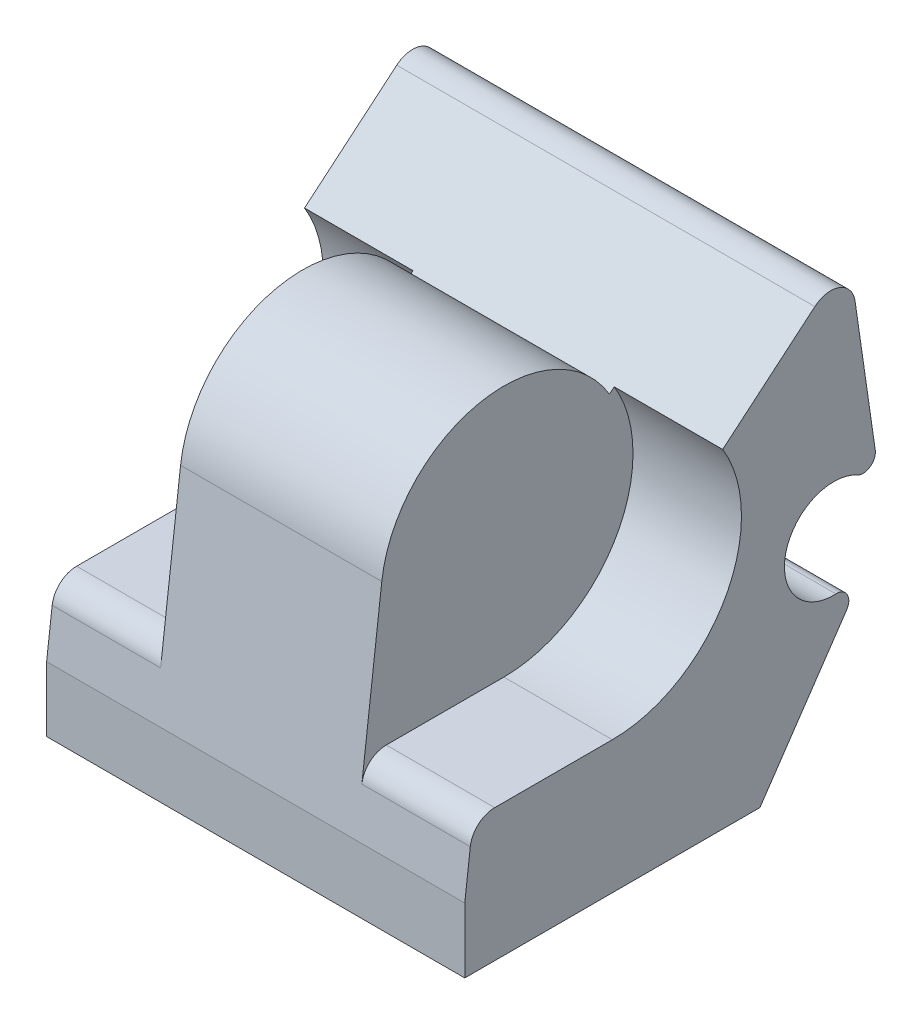
SolidWorks part; units mm, degrees
ref_plane "Front Plane" through (0, 0, 0) normal (0, 0, 1) x (1, 0, 0)
ref_plane "Top Plane" through (0, 0, 0) normal (0, 1, 0) x (1, 0, 0)
ref_plane "Right Plane" through (0, 0, 0) normal (1, 0, 0) x (0, 0, -1)
sketch "Sketch1" plane through (0, 0, 0) normal (1, 0, 0) x (0, 0, -1)
  line L0 (-15.761, 1.8989) -> (-19.05, -25.4)
  line L1 (15.761, 1.8989) -> (19.05, -25.4)
  line L2 (-19.05, -25.4) -> (-19.05, -33.782)
  line L3 (-19.05, -33.782) -> (19.05, -33.782)
  line L4 (19.05, -33.782) -> (19.05, -25.4)
  arc A0 (15.761, 1.8989) -> (-15.761, 1.8989) centre (0, 0) ccw
  circle A1 centre (0, 0) radius 15.875 construction
  dimension "D1" = 31.75
  dimension "D2" = 33.782
  dimension "D3" = 25.4
  dimension "D4" = 38.1
extrude "Boss-Extrude1" add sketch "Sketch1" along normal mid plane 53.975
sketch "Sketch2" plane through (0, 0, 0) normal (1, 0, 0) x (0, 0, -1)
  line L0 (3.9515, 0.0055) -> (13.6257, 8.1458) construction
  line L2 (0, 0) -> (3.9515, 0.0055) construction
  line L5 (24.1248, 18.0177) -> (24.6358, 17.4103) construction
  line L6 (34.8498, -7.5467) -> (31.3317, 16.7069)
  line L7 (26.1454, 18.6805) -> (30.5124, 22.3552) construction
  line L8 (30.5124, 22.3552) -> (31.3317, 16.7069) construction
  line L9 (33.8194, -12.0246) -> (19.05, -33.782)
  line L10 (19.05, -33.782) -> (19.05, -25.4)
  line L11 (11.2594, -12.2912) -> (3.9515, 0.0055) construction
  line L12 (0, 15.875) -> (0, 16.6688) construction
  line L13 (19.05, -25.4) -> (11.2594, -12.2912) construction
  line L14 (14.2406, 8.6632) -> (13.6257, 8.1458) construction
  line L15 (13.6257, 8.1458) -> (26.1454, 18.6805)
  line L17 (19.05, -25.4) -> (15.761, 1.8989)
  line L18 (19.05, -33.782) -> (19.05, -25.4) construction
  line L19 (15.761, 1.8989) -> (19.05, -25.4) construction
  line L20 (31.3422, 15.875) -> (5.0825, 15.875) construction
  line L21 (0, 0) -> (25.7629, 21.6783) construction
  circle A0 centre (28.5655, -8.4582) radius 3.175
  arc A2 (12.6144, 9.6381) -> (13.6257, 8.1458) centre (0, 0) ccw construction
  arc A3 (13.6158, 8.1624) -> (12.6144, 9.6381) centre (0, 0) ccw construction
  arc A4 (31.3317, 16.7069) -> (26.1454, 18.6805) centre (28.1896, 16.2512) ccw
  arc A5 (33.8194, -12.0246) -> (34.8498, -7.5467) centre (28.5655, -8.4582) ccw
  arc A6 (34.8498, -7.5467) -> (33.8194, -12.0246) centre (28.5655, -8.4582) ccw construction
  arc A7 (26.1454, 18.6805) -> (31.3317, 16.7069) centre (28.1896, 16.2512) ccw construction
  circle A9 centre (0, 0) radius 16.6688 construction
  arc A13 (12.6144, 9.6381) -> (13.6158, 8.1624) centre (0, 0) cw construction
  arc A14 (13.6257, 8.1458) -> (13.6158, 8.1624) centre (0, 0) ccw construction
  arc A17 (13.6257, 8.1458) -> (15.761, 1.8989) centre (0, 0) cw
  arc A18 (15.761, 1.8989) -> (-15.761, 1.8989) centre (0, 0) ccw construction
  arc A19 (13.6158, 8.1624) -> (13.6257, 8.1458) centre (0, 0) cw construction
  dimension "D3" = 6.35
  dimension "D8" = 6.35
  dimension "D9" = 12.7
  dimension "D1" = 2.54
  dimension "D2" = 8.4582
  dimension "D5" = 123.209
  dimension "D6" = 40
extrude "Boss-Extrude2" add sketch "Sketch2" along normal mid plane 53.975
ref_plane "Plane1" through (20.6375, 0, 0) normal (1, 0, 0) x (0, 0, -1)
ref_plane "Plane2" through (-21.9075, 0, 0) normal (-1, 0, 0) x (0, 0, 1)
sketch "Sketch3" plane through (26.9875, 0, 0) normal (1, 0, 0) x (0, 0, -1)
  line L1 (-15.761, 1.8989) -> (-19.05, -25.4) construction
  line L5 (-15.1826, -16.6687) -> (0, -16.6687)
  line L6 (-15.761, 1.8989) -> (-18.3348, -19.464)
  line L7 (14.2406, 8.6632) -> (13.6257, 8.1458)
  line L8 (26.1454, 18.6805) -> (13.6257, 8.1458) construction
  arc A0 (13.6257, 8.1458) -> (-15.761, 1.8989) centre (0, 0) ccw
  arc A2 (0, -16.6687) -> (14.2406, 8.6632) centre (0, 0) ccw
  arc A3 (-15.1826, -16.6687) -> (-18.3348, -19.464) centre (-15.1826, -19.8438) ccw
  arc A4 (14.2406, 8.6632) -> (-16.369, -3.1471) centre (0, 0) ccw construction
  arc A5 (-15.761, 1.8989) -> (13.6257, 8.1458) centre (0, 0) ccw construction
  arc A6 (-16.369, -3.1471) -> (0, -16.6687) centre (0, 0) ccw construction
  arc A7 (-18.3348, -19.464) -> (-15.1826, -16.6687) centre (-15.1826, -19.8438) ccw construction
  arc A8 (13.6257, 8.1458) -> (-15.761, 1.8989) centre (0, 0) ccw construction
  dimension "D1" = 0.7937
  dimension "D2" = 6.35
extrude "Cut-Extrude1" cut sketch "Sketch3" against normal blind 14
extrude "Cut-Extrude2" cut sketch "Sketch3<3>" along normal blind 14 from surface starting at face at (-26.9875, -6.1299, -11.5252)
sketch "Sketch3<3>" plane through (26.9875, 0, 0) normal (1, 0, 0) x (0, 0, -1) same geometry as "Sketch3"
sketch "Sketch4" plane through (26.9875, 0, 0) normal (1, 0, 0) x (0, 0, -1)
  line L0 (19.05, -33.782) -> (33.8194, -12.0246) construction
  line L1 (34.8498, -7.5467) -> (31.3317, 16.7069) construction
  line L2 (33.8194, -12.0246) -> (30.2529, -17.2785)
  line L3 (33.9382, -1.2624) -> (34.8498, -7.5467)
  arc A0 (33.8194, -12.0246) -> (34.8498, -7.5467) centre (28.5655, -8.4582) ccw
  arc A3 (31.6068, -2.8839) -> (33.9382, -1.2624) centre (32.3672, -1.4903) ccw
  arc A4 (30.2529, -17.2785) -> (28.8647, -14.8011) centre (28.9395, -16.3869) ccw
  arc A5 (33.9382, -1.2624) -> (31.6068, -2.8839) centre (32.3672, -1.4903) ccw construction
  arc A6 (28.8647, -14.8011) -> (30.2529, -17.2785) centre (28.9395, -16.3869) ccw construction
  arc A7 (28.8647, -14.8011) -> (33.8194, -12.0246) centre (28.5655, -8.4582) ccw construction
  arc A8 (34.8498, -7.5467) -> (31.6068, -2.8839) centre (28.5655, -8.4582) ccw construction
  arc A9 (31.6068, -2.8839) -> (28.8647, -14.8011) centre (28.5655, -8.4582) ccw
  arc A11 (33.8194, -12.0246) -> (34.8498, -7.5467) centre (28.5655, -8.4582) ccw construction
  dimension "D1" = 3.175
extrude "Cut-Extrude3" cut sketch "Sketch4" against normal blind 17.6276
extrude "Cut-Extrude4" cut sketch "Sketch5<3>" along normal blind 17.6276 from surface starting at face at (-26.9875, -11.2205, -8.6999)
sketch "Sketch5<3>" plane through (26.9875, 0, 0) normal (1, 0, 0) x (0, 0, -1) same geometry as "Sketch4"
